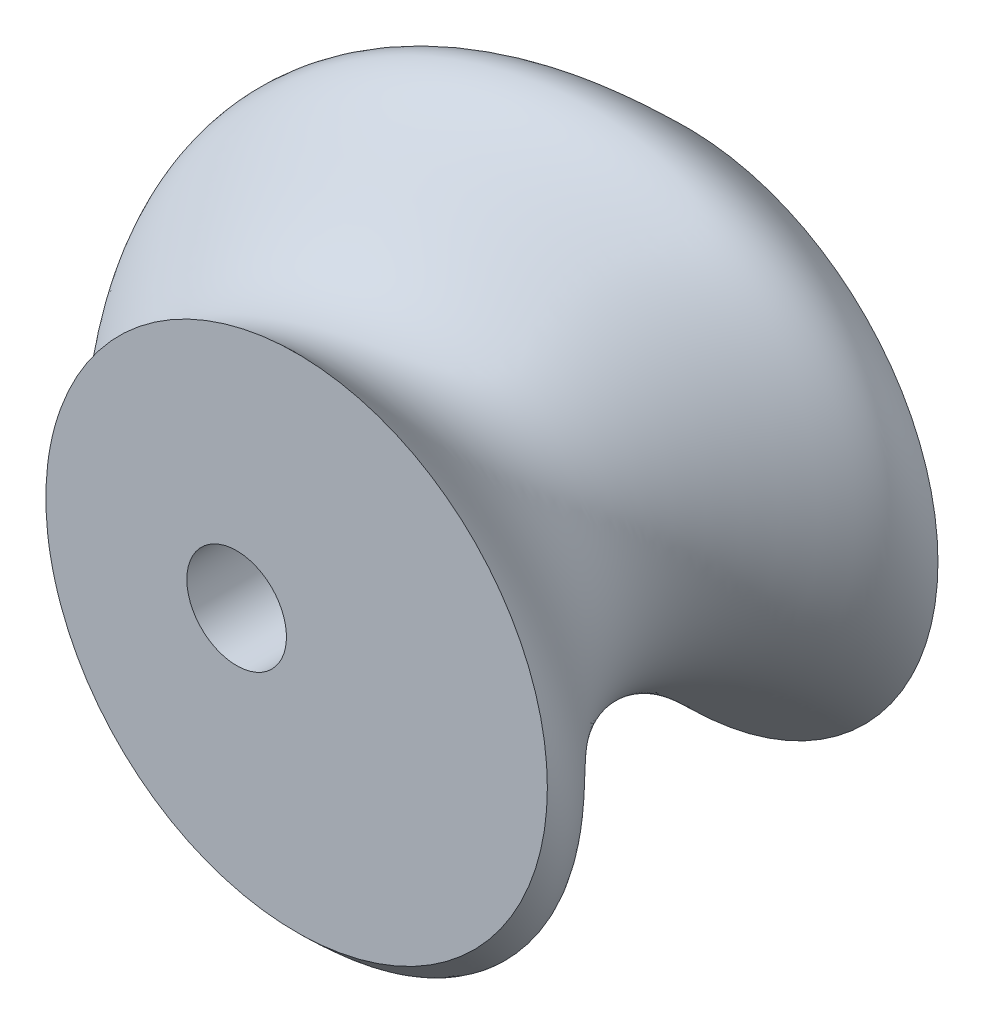
SolidWorks part; units mm, degrees
ref_plane "Ebene vorne" through (0, 0, 0) normal (0, 0, 1) x (1, 0, 0)
ref_plane "Ebene oben" through (0, 0, 0) normal (0, 1, 0) x (1, 0, 0)
ref_plane "Ebene rechts" through (0, 0, 0) normal (1, 0, 0) x (0, 0, -1)
sketch "Skizze2" plane through (0, 0, 0) normal (0, 0, 1) x (1, 0, 0)
  circle A0 centre (0, 0) radius 12.84
  dimension "D1" = 25.68
ref_plane "Ebene1" through (0, 0, 0) normal (0, 0, 1) x (1, 0, 0)
sketch "Skizze3" plane through (0, 0, 0) normal (0, 0, 1) x (1, 0, 0)
  circle A0 centre (-3.071, 0) radius 2.55
  point P0 (-3.071, 0)
  dimension "D2" = 5.1
  dimension "D1" = 3.071
curve "Spirale/Helix1" pitch 20 height 20 radius 2.55 centre (-3.071, 0, 0) axis (0, 0, 1) start towards (1, 0, 0)
sweep "Austragung1" add profiles "Skizze2" path "Spirale/Helix1"
sketch "Skizze5" plane through (0, 0, 20) normal (0, 0, 1) x (1, 0, 0)
  circle A0 centre (0, 0) radius 2.5
  dimension "D1" = 5
ref_plane "Ebene3" through (-0.521, 0, 0) normal (0, 0.6252, 0.7804) x (1, 0, 0)
extrude "Schnitt-Linear austragen2" cut sketch "Skizze3<2>" along normal blind 27
sketch "Skizze3<2>" plane through (0, 0, 0) normal (0, 0, 1) x (1, 0, 0) same geometry as "Skizze3"
ref_axis "Achse2" through (-3.071, 0, 20) along (0, 0, -1)
